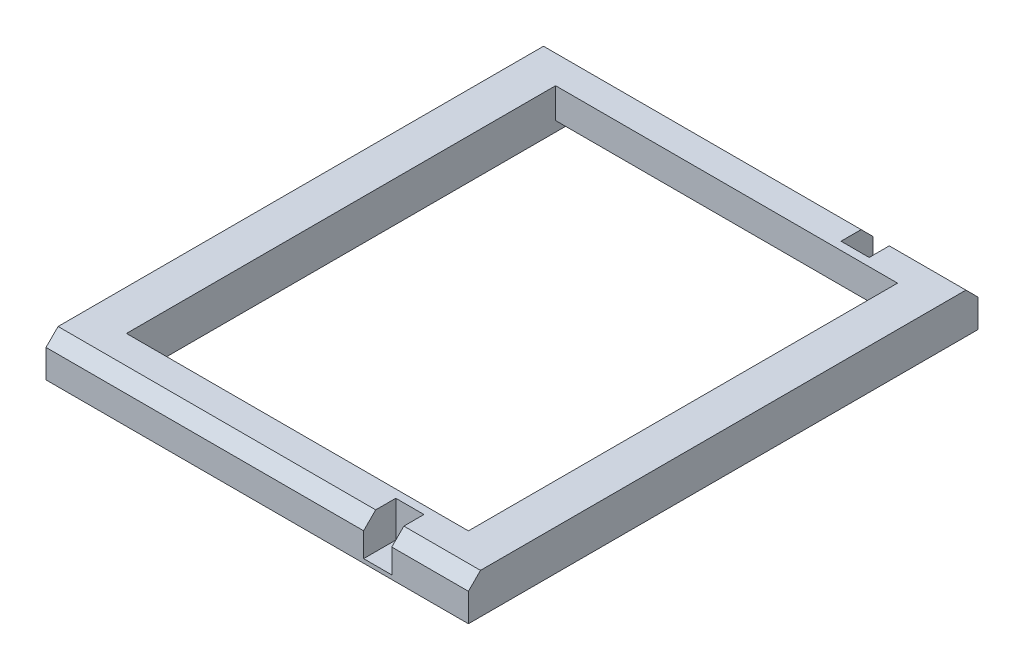
SolidWorks part; units mm, degrees
ref_plane "Front Plane" through (0, 0, 0) normal (0, 0, 1) x (1, 0, 0)
ref_plane "Top Plane" through (0, 0, 0) normal (0, 1, 0) x (1, 0, 0)
ref_plane "Right Plane" through (0, 0, 0) normal (1, 0, 0) x (0, 0, -1)
sketch "Sketch2" plane through (0, 0, 0) normal (0, 1, 0) x (1, 0, 0)
  line L1 (-66.675, -80.4333) -> (66.675, -80.4333)
  line L2 (-66.675, -80.4333) -> (-66.675, 80.4333)
  line L3 (-66.675, 80.4333) -> (66.675, 80.4333)
  line L4 (66.675, -80.4333) -> (66.675, 80.4333)
  line L5 (53.975, -67.7333) -> (-53.975, -67.7333)
  line L6 (53.975, -67.7333) -> (53.975, 67.7333)
  line L7 (53.975, 67.7333) -> (-53.975, 67.7333)
  line L8 (-53.975, -67.7333) -> (-53.975, 67.7333)
  point P4 (-66.675, 0)
  point P9 (0, -80.4333)
  point P11 (53.975, 0)
  point P12 (0, -67.7333)
  dimension "D1" = 12.7
  dimension "D2" = 12.7
  dimension "D3" = 160.8667
  dimension "D4" = 133.35
extrude "Boss-Extrude1" add sketch "Sketch2" along normal blind 12.7
sketch "Sketch3" plane through (0, 0, 0) normal (0, -1, 0) x (1, 0, 0)
  line L0 (-57.15, 76.2) -> (-60.325, 73.025)
  line L1 (-57.15, 76.2) -> (-60.325, 79.375)
  line L2 (-60.325, 73.025) -> (-63.5, 76.2)
  line L3 (-60.325, 79.375) -> (-63.5, 76.2)
  line L4 (-57.15, 76.2) -> (-63.5, 76.2) construction
  line L5 (-60.325, 73.025) -> (-60.325, 79.375) construction
  line L6 (57.15, 76.2) -> (53.975, 73.025)
  line L7 (57.15, 76.2) -> (53.975, 79.375)
  line L8 (53.975, 73.025) -> (50.8, 76.2)
  line L9 (53.975, 79.375) -> (50.8, 76.2)
  line L10 (57.15, 76.2) -> (50.8, 76.2) construction
  line L11 (53.975, 73.025) -> (53.975, 79.375) construction
  line L12 (57.15, -76.2) -> (53.975, -79.375)
  line L13 (57.15, -76.2) -> (53.975, -73.025)
  line L14 (53.975, -79.375) -> (50.8, -76.2)
  line L15 (53.975, -73.025) -> (50.8, -76.2)
  line L16 (57.15, -76.2) -> (50.8, -76.2) construction
  line L17 (53.975, -79.375) -> (53.975, -73.025) construction
  line L18 (-57.15, -76.2) -> (-60.325, -79.375)
  line L19 (-57.15, -76.2) -> (-60.325, -73.025)
  line L20 (-60.325, -79.375) -> (-63.5, -76.2)
  line L21 (-60.325, -73.025) -> (-63.5, -76.2)
  line L22 (-57.15, -76.2) -> (-63.5, -76.2) construction
  line L23 (-60.325, -79.375) -> (-60.325, -73.025) construction
  line L24 (-66.675, -80.4333) -> (-66.675, 80.4333) construction
  line L25 (66.675, -80.4333) -> (-66.675, -80.4333) construction
  line L26 (66.675, 80.4333) -> (66.675, -80.4333) construction
  line L28 (-66.675, 80.4333) -> (66.675, 80.4333) construction
  point P1 (-60.325, 76.2)
  point P2 (53.975, 76.2)
  point P3 (53.975, -76.2)
  point P8 (-60.325, -76.2)
  dimension "D1" = 6.35
  dimension "D2" = 4.2333
  dimension "D3" = 6.35
  dimension "D5" = 4.2333
  dimension "D6" = 12.7
extrude "Cut-Extrude1" cut sketch "Sketch3" against normal blind 6.35
chamfer "Chamfer4" distance 3.81 angle 45 2 edges at (0, 12.7, -80.4333) (0, 12.7, 80.4333)
chamfer "Chamfer1" distance 0.635 angle 45 32 edges at (-58.7375, 6.35, -77.7875) (-61.9125, 6.35, -77.7875) (-61.9125, 6.35, -74.6125) (-58.7375, 6.35, -74.6125) (55.5625, 6.35, 74.6125) (52.3875, 6.35, 74.6125) (52.3875, 6.35, 77.7875) (55.5625, 6.35, 77.7875) (-58.7375, 6.35, 74.6125) (-61.9125, 6.35, 74.6125) (-61.9125, 6.35, 77.7875) (-58.7375, 6.35, 77.7875) (-58.7375, 0, -74.6125) (-58.7375, 0, -77.7875) (-61.9125, 0, -77.7875) (-61.9125, 0, -74.6125) (52.3875, 0, -77.7875) (52.3875, 0, -74.6125) (55.5625, 0, -74.6125) (55.5625, 0, -77.7875) (55.5625, 6.35, -77.7875) (52.3875, 6.35, -77.7875) (55.5625, 6.35, -74.6125) (52.3875, 6.35, -74.6125) (52.3875, 0, 74.6125) (55.5625, 0, 74.6125) (55.5625, 0, 77.7875) (52.3875, 0, 77.7875) (-61.9125, 0, 74.6125) (-58.7375, 0, 74.6125) (-58.7375, 0, 77.7875) (-61.9125, 0, 77.7875)
chamfer "Chamfer2" distance 3.175 angle 45 3 edges at (0, 0, -67.7333) (0, 0, 67.7333) (53.975, 0, 0)
sketch "Sketch4" plane through (0, 0, 80.4333) normal (0, 0, 1) x (1, 0, 0)
  line L1 (33.5915, 1.27) -> (42.4815, 1.27)
  line L2 (33.5915, 1.27) -> (33.5915, 12.7)
  line L3 (33.5915, 12.7) -> (42.4815, 12.7)
  line L4 (42.4815, 1.27) -> (42.4815, 12.7)
  line L6 (66.675, 8.89) -> (66.675, 0) construction
  line L7 (-66.675, 12.7) -> (66.675, 12.7) construction
  dimension "D1" = 8.89
  dimension "D2" = 11.43
  dimension "D3" = 24.1935
extrude "Cut-Extrude2" cut sketch "Sketch4" against normal offset from surface (10.16 mm away) 2.54 up to face at (0, 7.9375, 67.7333)
sketch "Sketch5" plane through (0, 0, -80.4333) normal (0, 0, -1) x (-1, 0, 0)
  line L0 (-33.5915, 8.89) -> (-33.5915, 1.27) construction
  line L1 (-33.5915, 1.27) -> (-42.4815, 1.27)
  line L2 (-33.5915, 1.27) -> (-33.5915, 12.7)
  line L3 (-33.5915, 12.7) -> (-42.4815, 12.7)
  line L4 (-42.4815, 1.27) -> (-42.4815, 12.7)
  line L5 (-42.4815, 12.7) -> (-33.5915, 12.7) construction
  line L8 (-33.5915, 1.27) -> (-42.4815, 1.27) construction
extrude "Cut-Extrude3" cut sketch "Sketch5" against normal offset from surface (10.16 mm away) 2.54 up to face at (0, 7.9375, -67.7333)
